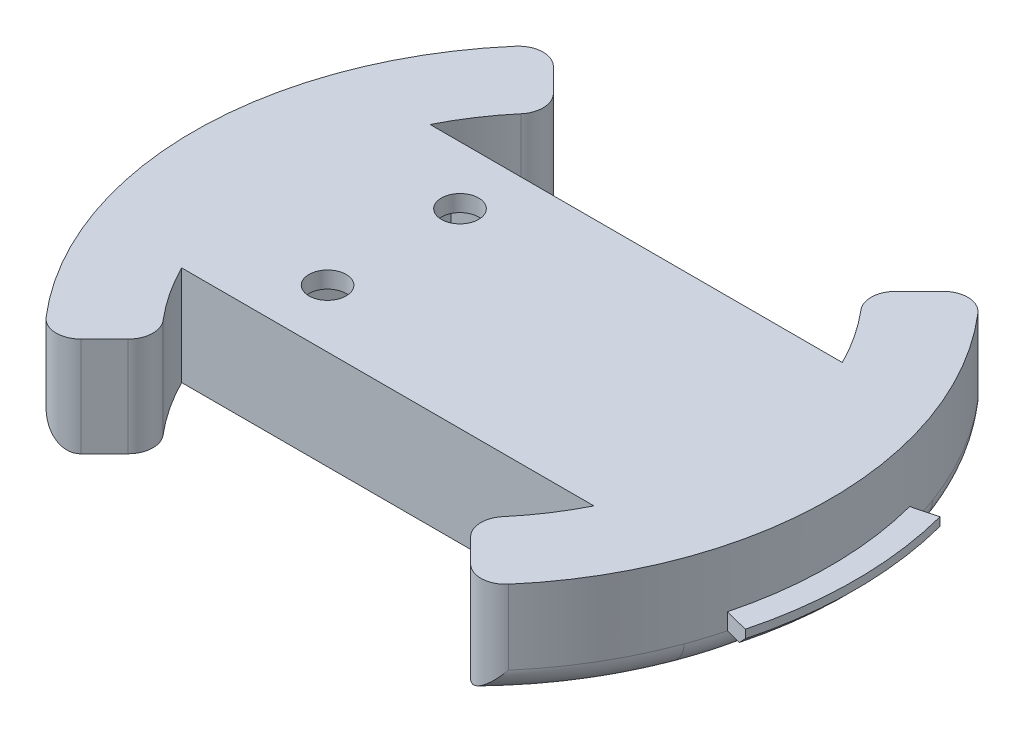
SolidWorks part; units mm, degrees
ref_plane "Front Plane" through (0, 0, 0) normal (0, 0, 1) x (1, 0, 0)
ref_plane "Top Plane" through (0, 0, 0) normal (0, 1, 0) x (1, 0, 0)
ref_plane "Right Plane" through (0, 0, 0) normal (1, 0, 0) x (0, 0, -1)
sketch "Sketch1" plane through (0, 0, 0) normal (0, 1, 0) x (1, 0, 0)
  line L0 (-144.0234, 0) -> (144.0234, 0) construction
  line L1 (-37.2787, 15) -> (34.2787, 15)
  line L2 (-37.2787, 15) -> (-37.2787, -15) construction
  line L3 (-37.2787, -15) -> (34.2787, -15)
  line L4 (34.2787, 15) -> (34.2787, -15) construction
  line L5 (-37.2787, 15) -> (34.2787, -15) construction
  line L6 (-37.2787, -15) -> (34.2787, 15) construction
  line L7 (-1.5, 15) -> (-1.5, -15) construction
  line L8 (-39.95, 85.2716) -> (-39.95, -85.2716) construction
  line L9 (36.95, 91.1525) -> (36.95, -91.1525) construction
  line L10 (0, 31.8261) -> (0, -31.8261) construction
  arc A0 (-37.2787, -15) -> (-37.2787, 15) centre (3.5, 0) cw
  arc A1 (34.2787, -15) -> (34.2787, 15) centre (-6.5, 0) ccw
  point P0 (-1.5, 0)
  point P9 (0, 0)
  point P14 (0, 0)
  point P18 (-39.95, 0)
  point P21 (36.95, 0)
  point P25 (0, 0)
  dimension "D1" = 43.45
  dimension "D2" = 76.9
  dimension "D3" = 30
  dimension "D4" = 1.5
extrude "Boss-Extrude1" add sketch "Sketch1" along normal mid plane 12
sketch "Sketch2" plane through (0, 6, 0) normal (0, 1, 0) x (1, 0, 0)
  line L0 (0, 0) -> (-39.95, 0) construction
  line L1 (-39.95, 6.25) -> (-39.95, -6.25) construction
  line L2 (-24.95, -6.25) -> (-54.95, -6.25)
  line L3 (-24.95, -6.25) -> (-24.95, 6.25)
  line L4 (-24.95, 6.25) -> (-54.95, 6.25)
  line L5 (-54.95, -6.25) -> (-54.95, 6.25)
  line L6 (-24.95, -6.25) -> (-54.95, 6.25) construction
  line L7 (-24.95, 6.25) -> (-54.95, -6.25) construction
  arc A0 (-37.2787, 15) -> (-37.2787, -15) centre (3.5, 0) ccw construction
  point P6 (-39.95, 0)
  point P16 (-39.95, 0)
  dimension "D1" = 15
  dimension "D2" = 12.5
extrude "Cut-Extrude1" [suppressed] cut sketch "Sketch2" against normal up to next
sketch "Sketch3" plane through (0, -6, 0) normal (0, -1, 0) x (1, 0, 0)
  line L0 (-15.7787, 15) -> (-15.7787, -15) construction
  line L1 (-37.2787, 15) -> (34.2787, 15) construction
  line L2 (34.2787, -15) -> (-37.2787, -15) construction
  line L3 (-37.2787, 15) -> (-37.2787, -15) construction
  line L4 (-9.2787, 9) -> (-22.2787, 9) construction
  line L5 (-22.2787, 9) -> (-22.2787, 15)
  line L6 (-22.2787, 15) -> (-9.2787, 15)
  line L7 (-9.2787, 15) -> (-9.2787, 9)
  line L8 (39.95, 0) -> (-39.95, 0) construction
  line L9 (-9.2787, -15) -> (-9.2787, -9)
  line L10 (-22.2787, -15) -> (-9.2787, -15)
  line L11 (-22.2787, -9) -> (-22.2787, -15)
  arc A0 (-9.2787, 9) -> (-22.2787, 9) centre (-15.7787, 9) cw
  arc A1 (-37.2787, 15) -> (-37.2787, -15) centre (3.5, 0) ccw construction
  arc A2 (-9.2787, -9) -> (-22.2787, -9) centre (-15.7787, -9) ccw
  point P17 (-15.7787, 9)
  point P23 (0, 0)
  dimension "D1" = 21.5
  dimension "D2" = 6
  dimension "D3" = 13
extrude "Cut-Extrude2" [suppressed] cut sketch "Sketch3" against normal offset from surface (8 mm away) 2
sketch "Sketch4" plane through (0, -6, 0) normal (0, -1, 0) x (1, 0, 0)
  line L2 (39.95, 0) -> (-39.95, 0) construction
  line L3 (-37.2787, 15) -> (34.2787, 15) construction
  circle A0 centre (-15.7787, 8) radius 2.25
  circle A1 centre (-15.7787, -8) radius 2.25
  arc A2 (-37.2787, 15) -> (-37.2787, -15) centre (3.5, 0) ccw construction
  circle A3 centre (12.7787, 0) radius 2.25 construction
  point P13 (0, 0)
  dimension "D1" = 4.5
  dimension "D2" = 21.5
  dimension "D3" = 7
  dimension "D4" = 21.5
extrude "Cut-Extrude3" cut sketch "Sketch4" against normal up to next
sketch "Sketch5" plane through (0, 0, 0) normal (0, 0, 1) x (1, 0, 0)
  line L1 (-39.95, 6) -> (-39.95, -6) construction
  line L5 (-37.2787, 6) -> (-39.95, 6) construction
  line L7 (-39.95, -1) -> (-39.95, 1)
  line L8 (-39.95, 1) -> (-40.95, 1)
  line L9 (-40.95, 1) -> (-40.95, 0)
  line L10 (-40.95, 0) -> (-39.95, -1)
  point P15 (-39.95, 0)
  dimension "D1" = 45
  dimension "D2" = 1
  dimension "D3" = 1
  dimension "D4" = 5
sketch "Sketch12" plane through (0, -6, 0) normal (0, -1, 0) x (1, 0, 0)
  line L1 (-22.2787, 13.4) -> (19.2787, 13.4)
  line L2 (-22.2787, 13.4) -> (-22.2787, -13.4)
  line L3 (-22.2787, -13.4) -> (19.2787, -13.4)
  line L4 (19.2787, 13.4) -> (19.2787, -13.4)
  line L6 (-37.2787, 15) -> (34.2787, 15) construction
  line L7 (34.2787, -15) -> (-37.2787, -15) construction
  dimension "D1" = 15
  dimension "D2" = 15
  dimension "D3" = 1.6
  dimension "D4" = 1.6
extrude "Cut-Extrude5" cut sketch "Sketch12" against normal offset from surface (10 mm away) 2 up to face at (-15.7787, 6, 10.25)
fillet "Fillet2" radius 3 2 edges at (36.95, -6, 0) (-39.95, -6, 0)
sketch "Sketch6" plane through (0, 0, 0) normal (0, 1, 0) x (1, 0, 0)
  arc A0 (-37.2787, 15) -> (-37.2787, -15) centre (3.5, 0) ccw construction
  arc A1 (-37.2787, 15) -> (-37.2787, -15) centre (3.5, 0) ccw
sweep "Sweep1" add profiles "Sketch5" path "Sketch6"
sketch "Sketch7" plane through (0, 6, 0) normal (0, 1, 0) x (1, 0, 0)
  line L0 (-42.0001, 0.7444) -> (-37.6222, 19.2556) construction
  line L1 (-39.8112, 10) -> (-30.2265, 10) construction
  line L2 (34.2787, 15) -> (-37.2787, 15) construction
  line L3 (-39.7568, 10.2301) -> (-38.7836, 10)
  line L4 (-30.2265, 5) -> (-40.6679, 5) construction
  line L5 (-39.5657, 14.6255) -> (-41.7701, -4.6255) construction
  line L6 (-39.6614, 5) -> (-40.6549, 5.1138)
  line L7 (0, 0) -> (-40.95, 0) construction
  line L8 (-39.6614, -5) -> (-40.6549, -5.1138)
  line L9 (-39.7568, -10.2301) -> (-38.7836, -10)
  line L10 (-37.2787, 15) -> (-38.2172, 15.3452) construction
  line L11 (-37.2787, -15) -> (-38.2172, -15.3452) construction
  line L12 (-37.2787, 15) -> (-38.2172, 15.3452)
  line L13 (-37.2787, -15) -> (-38.2172, -15.3452)
  arc A1 (-37.2787, 15) -> (-37.2787, -15) centre (3.5, 0) ccw construction
  arc A2 (-37.2787, 15) -> (-37.2787, -15) centre (3.5, 0) ccw construction
  arc A3 (-38.2172, 15.3452) -> (-38.2172, -15.3452) centre (3.5, 0) ccw construction
  arc A4 (-38.2172, 15.3452) -> (-38.2172, -15.3452) centre (3.5, 0) ccw
  arc A5 (-37.2787, 15) -> (-37.2787, -15) centre (3.5, 0) ccw
  point P6 (-39.8112, 10)
  point P20 (-40.6679, 5)
  point P33 (-39.8112, -10)
  arc M11 (-37.2787, 15) -> (-37.2787, -15) centre (3.5, 0) ccw
  dimension "D1" = 5
  dimension "D2" = 90
  dimension "D3" = 90
  dimension "D4" = 5
extrude "Cut-Extrude4" cut sketch "Sketch7" against normal through all contours L12 A4 L3 M11 | L6 A4 L8 M11 | L9 A4 L13 M11 region at (-38.5616, 6, -12.6596) region at (-40.3545, 6, 0) region at (-38.5616, 6, 12.6596)
sketch "Sketch8" plane through (0, 0, 0) normal (0, 1, 0) x (1, 0, 0)
  line L0 (-37.2787, 15) -> (34.2787, 15) construction
  line L1 (-1.5, 15) -> (-1.5, -15) construction
  line L2 (-37.2787, -15) -> (34.2787, -15) construction
ref_plane "Middle" through (-1.5, 0, 0) normal (1, 0, 0) x (0, 0, -1)
sketch "Sketch9" plane through (0, 0, 0) normal (0, 0, 1) x (1, 0, 0)
  line L0 (39.95, -2) -> (38.95, -3)
  line L1 (39.95, -1) -> (36.95, -1)
  line L2 (36.95, -3) -> (36.95, 6) construction
  line L3 (39.95, -2) -> (39.95, -1)
  line L4 (38.95, -3) -> (36.95, -3)
  line L5 (36.95, -3) -> (36.95, -1)
  dimension "D1" = 3
  dimension "D2" = 2
  dimension "D3" = 1
  dimension "D4" = 135
sketch "Sketch10" plane through (0, 0, 0) normal (0, 1, 0) x (1, 0, 0)
  line L0 (24.9894, 11) -> (45.9582, 11) construction
  line L1 (24.9894, -11) -> (48.2937, -11) construction
  line L2 (-37.2787, -15) -> (34.2787, -15) construction
  line L3 (34.2787, 15) -> (-37.2787, 15) construction
  arc A0 (34.2787, -15) -> (34.2787, 15) centre (-6.5, 0) ccw construction
  arc A1 (35.5345, -11) -> (35.5345, 11) centre (-6.5, 0) ccw
  dimension "D1" = 4
  dimension "D2" = 4
sweep "Sweep2" add profiles "Sketch9" path "Sketch10"
sketch "Sketch11" plane through (0, 0, 0) normal (0, 1, 0) x (1, 0, 0)
  line L2 (-27.2238, 30.7238) -> (-20.1527, 23.6527)
  line L3 (34.2787, 15) -> (-37.2787, 15) construction
  line L4 (-39.95, 0) -> (46.95, 0) construction
  line L5 (-37.2787, 15) -> (-26.3982, 15)
  line L8 (17.1527, 23.6527) -> (24.2238, 30.7238)
  line L9 (34.2787, 15) -> (23.3982, 15)
  line L10 (34.2787, -15) -> (23.3982, -15)
  line L11 (17.1527, -23.6527) -> (24.2238, -30.7238)
  line L12 (-37.2787, -15) -> (-26.3982, -15)
  line L13 (-27.2238, -30.7238) -> (-20.1527, -23.6527)
  circle A4 centre (3.5, 0) radius 43.45 construction
  arc A5 (-37.2787, 15) -> (-37.2787, -15) centre (3.5, 0) ccw construction
  circle A6 centre (-6.5, 0) radius 43.45 construction
  arc A7 (35.5345, -11) -> (35.5345, 11) centre (-6.5, 0) ccw construction
  circle A8 centre (-6.5, 0) radius 33.45 construction
  circle A9 centre (3.5, 0) radius 33.45 construction
  arc A10 (-26.3982, 15) -> (-20.1527, 23.6527) centre (3.5, 0) cw
  arc A11 (-37.2787, 15) -> (-27.2238, 30.7238) centre (3.5, 0) cw
  arc A14 (23.3982, 15) -> (17.1527, 23.6527) centre (-6.5, 0) ccw
  arc A15 (34.2787, 15) -> (24.2238, 30.7238) centre (-6.5, 0) ccw
  arc A16 (34.2787, -15) -> (24.2238, -30.7238) centre (-6.5, 0) cw
  arc A17 (23.3982, -15) -> (17.1527, -23.6527) centre (-6.5, 0) cw
  arc A18 (-37.2787, -15) -> (-27.2238, -30.7238) centre (3.5, 0) ccw
  arc A19 (-26.3982, -15) -> (-20.1527, -23.6527) centre (3.5, 0) ccw
  point P26 (-6.5, 0)
  point P27 (0, 0)
  dimension "D3" = 45
  dimension "D4" = 45
  dimension "D1" = 10
  dimension "D2" = 10
extrude "Boss-Extrude2" add sketch "Sketch11" along normal up to surface (6 mm away) and the other way up to surface (6 mm away) up to face at (-15.7787, 6, 10.25) other way up to face at (-1.5, -6, 0)
fillet "Fillet1" radius 3 12 edges at (17.1527, 0, -23.6527) (24.2238, 0, -30.7238) (-20.1527, 0, -23.6527) (-27.2238, 0, -30.7238) (-20.1527, 0, 23.6527) (-27.2238, 0, 30.7238) (30.1055, -6, 23.4082) (17.1527, 0, 23.6527) (24.2238, 0, 30.7238) (-33.1055, -6, 23.4082) (-33.1055, -6, -23.4082) (30.1055, -6, -23.4082)
equation "\"D1@Sketch1\"=86.9/2"
